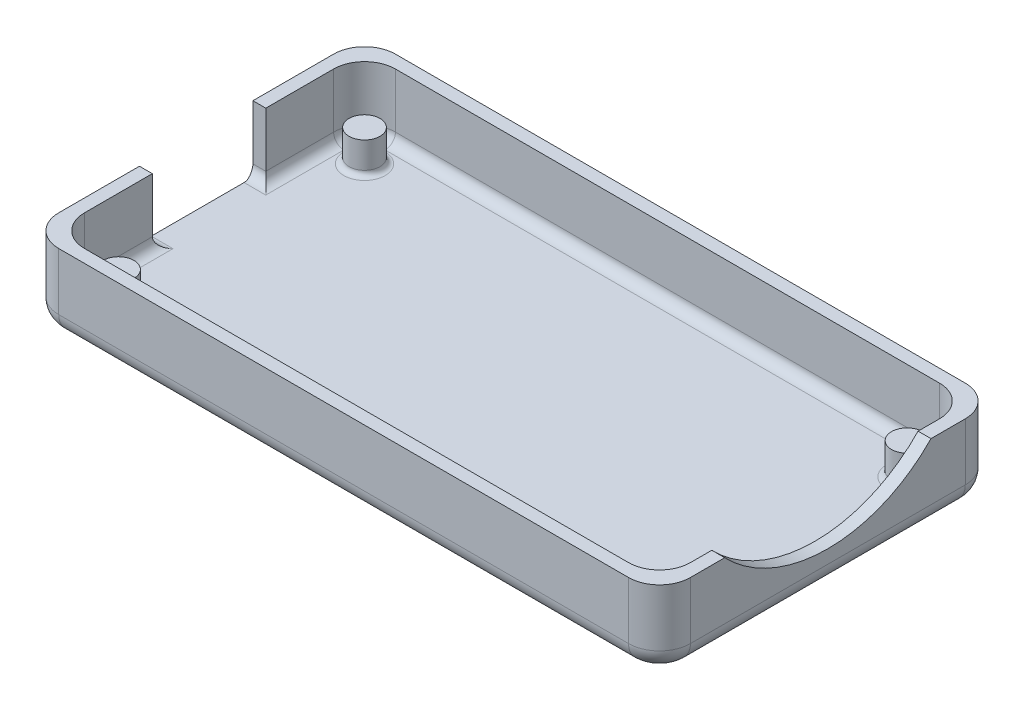
SolidWorks part; units mm, degrees
ref_plane "Front Plane" through (0, 0, 0) normal (0, 0, 1) x (1, 0, 0)
ref_plane "Top Plane" through (0, 0, 0) normal (0, 1, 0) x (1, 0, 0)
ref_plane "Right Plane" through (0, 0, 0) normal (1, 0, 0) x (0, 0, -1)
sketch "Sketch2" plane through (0, 0, 0) normal (0, 1, 0) x (1, 0, 0)
  line L0 (-52.9, -30.15) -> (-0.15, -30.15)
  line L1 (-55.9, -27.15) -> (-55.9, -3)
  line L2 (-52.9, 0) -> (-0.15, 0)
  line L3 (2.85, -27.15) -> (2.85, -3)
  line L4 (-54.15, 1.25) -> (1.1, 1.25)
  line L5 (-57.15, -1.75) -> (-57.15, -28.4)
  line L6 (-54.15, -31.4) -> (1.1, -31.4)
  line L7 (4.1, -1.75) -> (4.1, -28.4)
  line L12 (2.85, 0) -> (-55.9, 0) construction
  line L13 (-55.9, 0) -> (-55.9, -30.15) construction
  line L14 (-55.9, -30.15) -> (2.85, -30.15) construction
  line L15 (2.85, -30.15) -> (2.85, 0) construction
  arc A0 (-52.9, -30.15) -> (-55.9, -27.15) centre (-52.9, -27.15) cw
  arc A1 (-0.15, -30.15) -> (2.85, -27.15) centre (-0.15, -27.15) ccw
  arc A2 (-0.15, 0) -> (2.85, -3) centre (-0.15, -3) cw
  arc A3 (-55.9, -3) -> (-52.9, 0) centre (-52.9, -3) cw
  arc A4 (-57.15, -28.4) -> (-54.15, -31.4) centre (-54.15, -28.4) ccw
  arc A5 (1.1, -31.4) -> (4.1, -28.4) centre (1.1, -28.4) ccw
  arc A6 (1.1, 1.25) -> (4.1, -1.75) centre (1.1, -1.75) cw
  arc A7 (-54.15, 1.25) -> (-57.15, -1.75) centre (-54.15, -1.75) ccw
  dimension "D5" = 3
  dimension "D6" = 3
  dimension "D1" = 1.25
  dimension "D2" = 1.25
  dimension "D3" = 1.25
  dimension "D4" = 1.25
  dimension "D7" = 58.75
  dimension "D8" = 30.15
extrude "Boss-Extrude2" add sketch "Sketch2" along normal blind 7.55
sketch "Sketch3" plane through (0, 0, 0) normal (0, 1, 0) x (1, 0, 0)
  line L0 (-55.9, 0) -> (-55.9, -30.15)
  line L1 (-55.9, -30.15) -> (2.85, -30.15)
  line L2 (2.85, -30.15) -> (2.85, 0)
  line L3 (2.85, 0) -> (-55.9, 0)
  line L6 (2.85, -27.15) -> (2.85, -3) construction
  line L7 (-0.15, 0) -> (-52.9, 0) construction
  line L8 (-52.9, -30.15) -> (-0.15, -30.15) construction
  line L9 (-55.9, -3) -> (-55.9, -27.15) construction
extrude "Boss-Extrude3" add sketch "Sketch3" along normal blind 1.25
sketch "Sketch5" plane through (0, 1.25, 0) normal (0, 1, 0) x (1, 0, 0)
  line L0 (-26.525, 0) -> (-26.525, -30.15) construction
  line L1 (-0.15, 0) -> (-52.9, 0) construction
  line L2 (-52.9, -30.15) -> (-0.15, -30.15) construction
  line L3 (-55.9, -15.075) -> (2.85, -15.075) construction
  line L4 (-55.9, -3) -> (-55.9, -27.15) construction
  line L5 (2.85, -27.15) -> (2.85, -3) construction
  line L7 (-0.15, -30) -> (-52.75, -30)
  line L8 (2.85, -27) -> (2.85, -3.15)
  line L10 (-55.75, -27) -> (-55.75, -3.15)
  line L11 (2.85, -30) -> (-56.1889, -0.0032) construction
  line L12 (2.8174, -0.0901) -> (-55.75, -30) construction
  arc A0 (-0.15, -30) -> (2.85, -27) centre (-0.15, -27) ccw
  arc A1 (2.85, -3.15) -> (-0.15, -0.15) centre (-0.15, -3.15) ccw
  arc A2 (-52.75, -0.15) -> (-55.75, -3.15) centre (-52.75, -3.15) ccw
  arc A3 (-52.75, -30) -> (-55.75, -27) centre (-52.75, -27) cw
  circle A4 centre (-52.75, -3.15) radius 1.5
  circle A5 centre (-0.15, -3.15) radius 1.5
  circle A6 centre (-0.15, -27) radius 1.5
  circle A7 centre (-52.75, -27) radius 1.5
  point P12 (-26.525, -15.075)
  dimension "D3" = 3
  dimension "D4" = 3
  dimension "D1" = 30
  dimension "D2" = 58.6
  dimension "D5" = 2
extrude "Boss-Extrude4" add sketch "Sketch5" along normal blind 3.05 contours A4 | A5 | A6 | A7 region at (-52.75, 1.25, 3.15) region at (-0.15, 1.25, 3.15) region at (-0.15, 1.25, 27) region at (-52.75, 1.25, 27)
fillet "Fillet1" radius 0.5 4 edges at (-0.15, 1.25, 28.5) (-52.75, 1.25, 28.5) (-0.15, 1.25, 4.65) (-52.75, 1.25, 4.65)
fillet "Fillet4" radius 2 8 edges at (-26.525, 0, 31.4) (3.2213, 0, 30.5213) (4.1, 0, 15.075) (3.2213, 0, -0.3713) (-26.525, 0, -1.25) (-56.2713, 0, -0.3713) (-57.15, 0, 15.075) (-56.2713, 0, 30.5213)
sketch "Sketch7" plane through (-57.15, 0, 0) normal (-1, 0, 0) x (0, 0, 1)
  line L1 (1.75, 7.55) -> (28.4, 7.55) construction
  line L6 (9.575, 7.55) -> (9.575, 1.25)
  line L7 (9.575, 1.25) -> (20.575, 1.25)
  line L8 (20.575, 1.25) -> (20.575, 7.55)
  line L9 (15.075, 7.55) -> (15.075, 2) construction
  line L10 (1.75, 2) -> (28.4, 2) construction
  line L11 (9.575, 7.55) -> (20.575, 7.55)
  point P11 (15.075, 1.25)
  dimension "D1" = 11
  dimension "D2" = 6.3
extrude "Cut-Extrude1" cut sketch "Sketch7" against normal blind 2
fillet "Fillet7" radius 1 9 edges at (-55.9, 1.25, 23.8625) (-26.525, 1.25, 30.15) (2.85, 1.25, 15.075) (-55.9, 1.25, 6.2875) (-26.525, 1.25, 0) (1.9713, 1.25, 0.8787) (1.9713, 1.25, 29.2713) (-55.0213, 1.25, 29.2713) (-55.0213, 1.25, 0.8787)
sketch "Sketch8" plane through (4.1, 0, 0) normal (1, 0, 0) x (0, 0, -1)
  line L0 (-28.4, 7.55) -> (-1.75, 7.55) construction
  line L1 (-15.075, 7.55) -> (-15.075, 2) construction
  line L2 (-28.4, 2) -> (-1.75, 2) construction
  line L3 (-30.075, 7.55) -> (-0.075, 7.55)
  line L4 (-25.075, 7.55) -> (-5.075, 7.55)
  arc A0 (-25.075, 7.55) -> (-5.075, 7.55) centre (-15.075, 17.1897) ccw
  point P9 (-15.075, 3.3)
  point P15 (-15.075, 7.55)
  dimension "D1" = 4.25
  dimension "D2" = 30
  dimension "D3" = 5
extrude "Cut-Extrude2" cut sketch "Sketch8" against normal blind 2 contours L1 L4 A0 | L3 L1 A0 region at (4.1, 5.8255, 11.2346) region at (4.1, 5.8255, 18.9154)
fillet "Fillet8" radius 1 2 edges at (-55.952, 1.25, 20.575) (-55.952, 1.25, 9.575)
